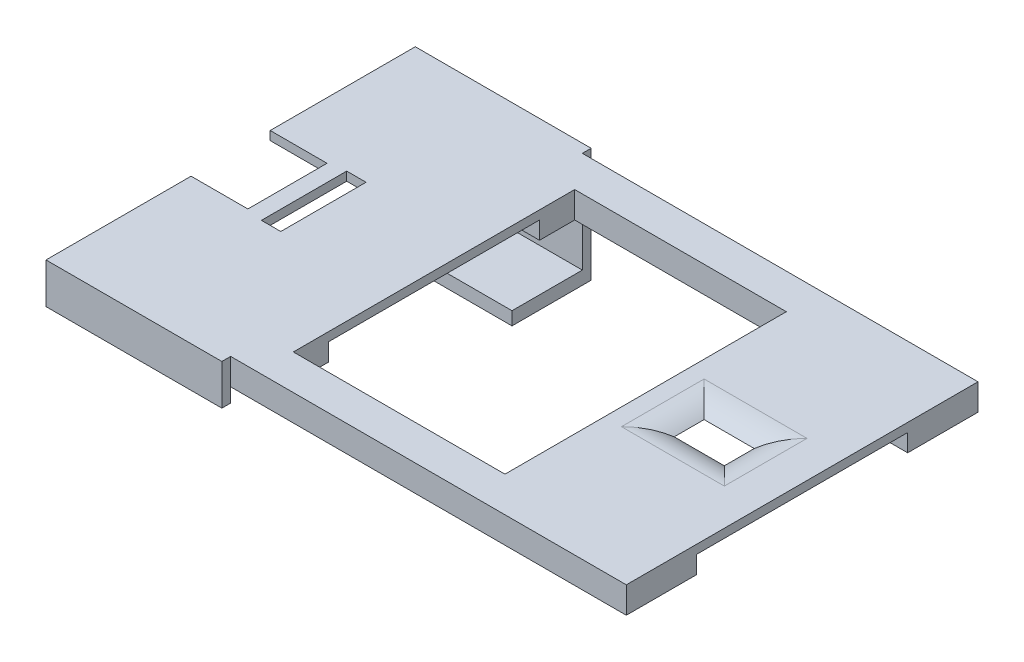
SolidWorks part; units mm, degrees
ref_plane "Front Plane" through (0, 0, 0) normal (0, 0, 1) x (1, 0, 0)
ref_plane "Top Plane" through (0, 0, 0) normal (0, 1, 0) x (1, 0, 0)
ref_plane "Right Plane" through (0, 0, 0) normal (1, 0, 0) x (0, 0, -1)
sketch "Sketch1" plane through (0, 0, 0) normal (0, 1, 0) x (1, 0, 0)
  line L0 (23.13, 29) -> (23.13, 36)
  line L1 (0, 0) -> (65, 0)
  line L2 (0, 0) -> (0, 40)
  line L3 (0, 40) -> (65, 40)
  line L4 (65, 0) -> (65, 40)
  line L5 (52.15, 18.3) -> (57.85, 18.3)
  line L6 (52.15, 18.3) -> (52.15, 21.7)
  line L7 (52.15, 21.7) -> (57.85, 21.7)
  line L8 (57.85, 18.3) -> (57.85, 21.7)
  line L9 (-0.89, 24.5) -> (6.46, 24.5)
  line L10 (-0.89, 24.5) -> (-0.89, 15.5)
  line L11 (-0.89, 15.5) -> (6.46, 15.5)
  line L12 (6.46, 24.5) -> (6.46, 15.5)
  line L13 (8.35, 15.15) -> (10.55, 15.15)
  line L14 (8.35, 15.15) -> (8.35, 24.85)
  line L15 (8.35, 24.85) -> (10.55, 24.85)
  line L16 (10.55, 15.15) -> (10.55, 24.85)
  line L17 (23.13, 29) -> (47.2, 29) construction
  line L18 (23.13, 29) -> (23.13, 11)
  line L19 (23.13, 11) -> (47.2, 11) construction
  line L20 (47.2, 29) -> (47.2, 11)
  line L21 (23.13, 36) -> (47.2, 36)
  line L22 (47.2, 36) -> (47.2, 29)
  line L23 (23.13, 11) -> (23.13, 4)
  line L24 (23.13, 4) -> (47.2, 4)
  line L25 (47.2, 4) -> (47.2, 11)
  dimension "D1" = 65
  dimension "D2" = 40
  dimension "D3" = 4
  dimension "D4" = 4
extrude "Boss-Extrude2" add sketch "Sketch1" along normal blind 3 contours L9 L12 L11 L2 L1 L4 L3 L25 L24 L23 L18 L0 L21 L22 L20 L16 L13 L14 L15 L8 L5 L6 L7 region at (0.7632, 0, -7.75)
sketch "Sketch3" plane through (23.13, 0, 0) normal (1, 0, 0) x (0, 0, -1)
  line L0 (11, -0.0081) -> (8, 0)
  line L1 (11, -0.4581) -> (11, 0.4419) construction
  line L2 (36, 0) -> (4, 0) construction
  line L3 (8, 0) -> (8, 2)
  line L4 (8, 2) -> (32, 2)
  line L5 (32, 2) -> (32, 0)
  line L6 (32, 0) -> (11, -0.0081)
  line L8 (29, -0.4581) -> (29, 0.4419) construction
  dimension "D1" = 3
  dimension "D2" = 3
  dimension "D3" = 2
extrude "Cut-Extrude2" cut sketch "Sketch3" against normal through all and the other way through all
fillet "Fillet1" radius 5 4 edges at (55, 3, -18.3) (57.85, 3, -20) (52.15, 3, -20) (55, 3, -21.7)
sketch "Sketch4" plane through (0, 0, -40) normal (0, 0, -1) x (-1, 0, 0)
  line L0 (0, 3) -> (-65, 3) construction
  line L1 (0, 0) -> (-20, 0)
  line L2 (0, 0) -> (0, 3)
  line L3 (0, 3) -> (-20, 3)
  line L4 (-20, 0) -> (-20, 3)
  dimension "D1" = 20
extrude "Boss-Extrude3" add sketch "Sketch4" along normal blind 1
sketch "Sketch5" plane through (0, 0, 0) normal (0, -1, 0) x (1, 0, 0)
  line L1 (0, -41) -> (20, -41)
  line L2 (0, -41) -> (0, -40)
  line L3 (0, -40) -> (20, -40)
  line L4 (20, -41) -> (20, -40)
extrude "Boss-Extrude4" add sketch "Sketch5" along normal blind 10
sketch "Sketch6" plane through (0, 0, -40) normal (0, 0, 1) x (1, 0, 0)
  line L0 (20, -10) -> (20, 0) construction
  line L1 (0, -10) -> (20, -10)
  line L2 (0, -10) -> (0, -8.5)
  line L3 (0, -8.5) -> (20, -8.5)
  line L4 (20, -10) -> (20, -8.5)
  dimension "D1" = 1.5
extrude "Boss-Extrude5" add sketch "Sketch6" along normal blind 8
sketch "Sketch7" plane through (0, 0, 0) normal (0, 0, 1) x (1, 0, 0)
  line L0 (0, 3) -> (65, 3) construction
  line L1 (0, 0) -> (20, 0)
  line L2 (0, 0) -> (0, 3)
  line L3 (0, 3) -> (20, 3)
  line L4 (20, 0) -> (20, 3)
  dimension "D1" = 20
extrude "Boss-Extrude6" add sketch "Sketch7" along normal blind 1
sketch "Sketch8" plane through (0, 0, 0) normal (0, -1, 0) x (1, 0, 0)
  line L1 (20, 1) -> (0, 1)
  line L2 (20, 1) -> (20, 0)
  line L3 (20, 0) -> (0, 0)
  line L4 (0, 1) -> (0, 0)
extrude "Boss-Extrude7" add sketch "Sketch8" along normal blind 1.6
